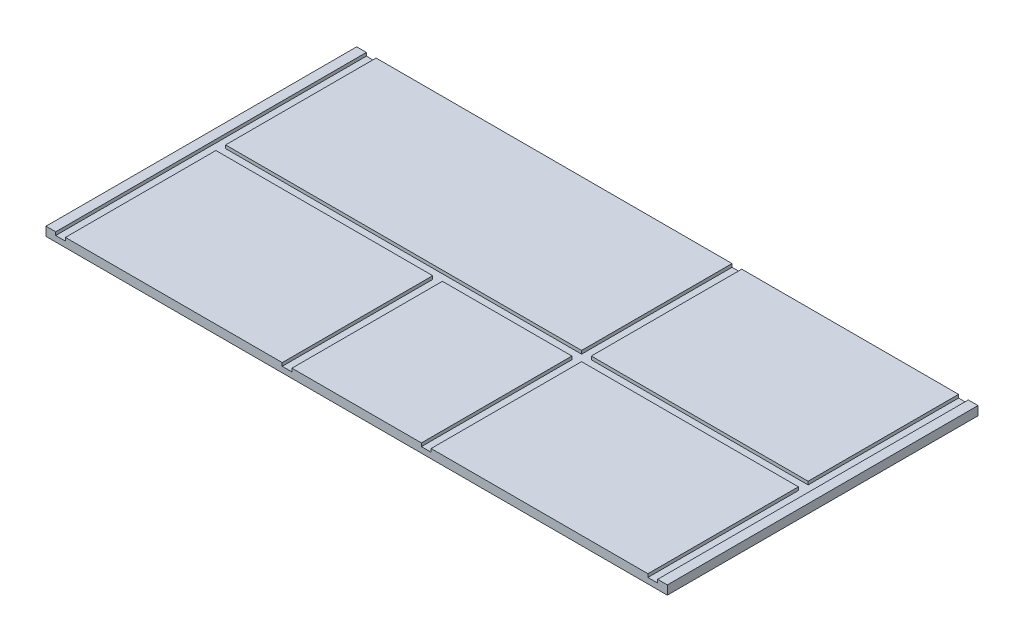
SolidWorks part; units mm, degrees
material "Cedar"
ref_plane "Front Plane" through (0, 0, 0) normal (0, 0, 1) x (1, 0, 0)
ref_plane "Top Plane" through (0, 0, 0) normal (0, 1, 0) x (1, 0, 0)
ref_plane "Right Plane" through (0, 0, 0) normal (1, 0, 0) x (0, 0, -1)
sketch "Sketch1" plane through (0, 0, 0) normal (0, 1, 0) x (1, 0, 0)
  line L1 (-609.6, -304.8) -> (609.6, -304.8)
  line L2 (-609.6, -304.8) -> (-609.6, 304.8)
  line L3 (-609.6, 304.8) -> (609.6, 304.8)
  line L4 (609.6, -304.8) -> (609.6, 304.8)
  line L5 (-609.6, -304.8) -> (609.6, 304.8) construction
  line L6 (-609.6, 304.8) -> (609.6, -304.8) construction
  point P0 (0, 0)
  dimension "D1" = 1219.2
  dimension "D2" = 609.6
extrude "Boss-Extrude1" add sketch "Sketch1" along normal blind 17.4752
sketch "Sketch2" plane through (0, 17.4752, 0) normal (0, 1, 0) x (1, 0, 0)
  line L0 (609.6, 304.8) -> (-609.6, 304.8) construction
  line L1 (-590.55, 304.8) -> (-571.5, 304.8)
  line L2 (-590.55, 304.8) -> (-590.55, -304.8)
  line L3 (-590.55, -304.8) -> (-571.5, -304.8)
  line L4 (-571.5, 304.8) -> (-571.5, 9.525)
  line L5 (-609.6, -304.8) -> (609.6, -304.8) construction
  line L7 (-571.5, 9.525) -> (127, 9.525)
  line L8 (-571.5, 9.525) -> (-571.5, -9.525) construction
  line L9 (-571.5, -9.525) -> (-146.05, -9.525)
  line L12 (590.55, 304.8) -> (571.5, 304.8)
  line L13 (590.55, 304.8) -> (590.55, -304.8)
  line L14 (590.55, -304.8) -> (571.5, -304.8)
  line L15 (571.5, 304.8) -> (571.5, 9.525)
  line L17 (-146.05, -9.525) -> (-127, -9.525) construction
  line L18 (-146.05, -9.525) -> (-146.05, -304.8)
  line L19 (-146.05, -304.8) -> (-127, -304.8)
  line L20 (-127, -9.525) -> (-127, -304.8)
  line L21 (-571.5, -9.525) -> (-571.5, -304.8)
  line L23 (127, -9.525) -> (127, -304.8)
  line L24 (127, -304.8) -> (146.05, -304.8)
  line L25 (146.05, -9.525) -> (146.05, -304.8)
  line L26 (-127, -9.525) -> (127, -9.525)
  line L27 (0, 0) -> (0, -9.525) construction
  line L28 (571.5, -9.525) -> (571.5, -304.8)
  line L29 (146.05, -9.525) -> (571.5, -9.525)
  line L30 (-590.55, 304.8) -> (-609.6, 304.8) construction
  line L31 (590.55, 304.8) -> (609.6, 304.8) construction
  line L32 (-609.6, 304.8) -> (-609.6, -304.8) construction
  line L33 (146.05, 9.525) -> (571.5, 9.525)
  line L35 (127, 9.525) -> (127, 304.8)
  line L36 (127, 304.8) -> (146.05, 304.8)
  line L37 (146.05, 9.525) -> (146.05, 304.8)
  line L38 (-571.5, 0) -> (-609.6, 0) construction
  dimension "D1" = 19.05
  dimension "D3" = 425.45
  dimension "D4" = 254
  dimension "D5" = 19.05
extrude "Cut-Extrude1" cut sketch "Sketch2" against normal blind 6.35
